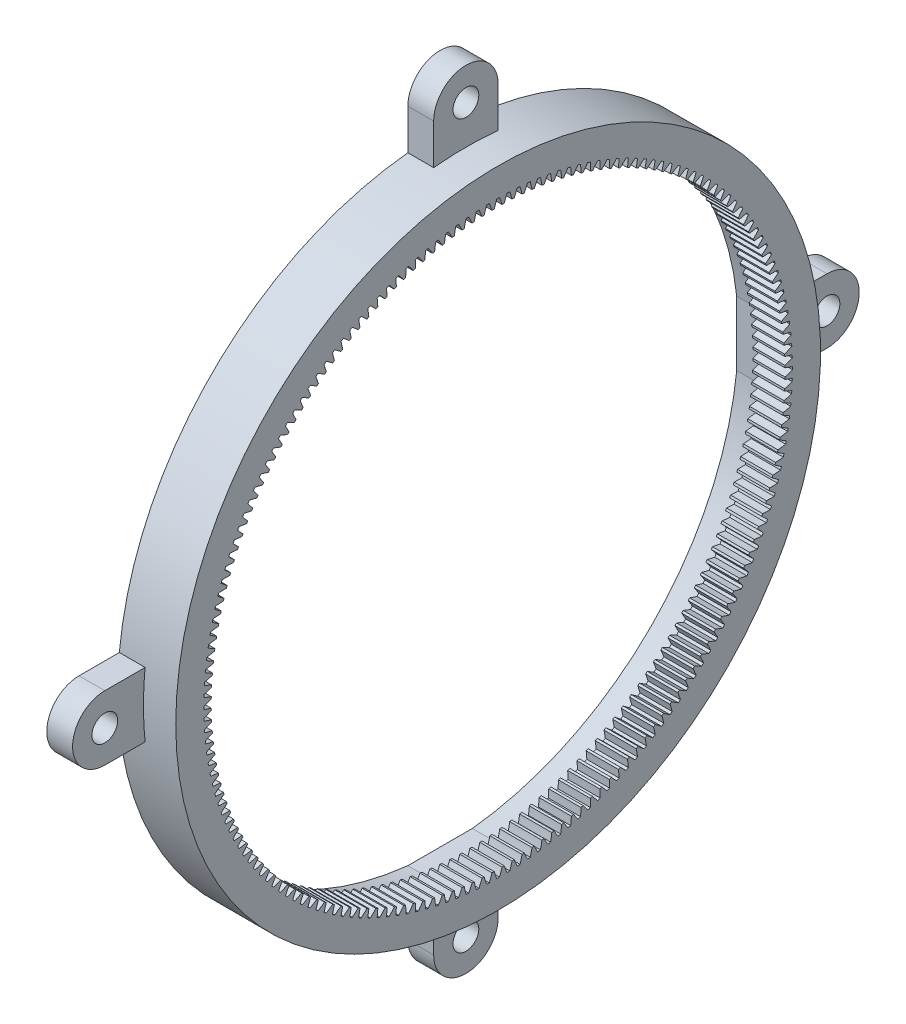
SolidWorks part; units mm, degrees
ref_plane "Plane1" through (0, 0, 0) normal (0, 0, 1) x (1, 0, 0)
ref_plane "Plane2" through (0, 0, 0) normal (0, 1, 0) x (1, 0, 0)
ref_plane "Plane3" through (0, 0, 0) normal (1, 0, 0) x (0, 0, -1)
other "Configuration Table"
sketch "HoldingSke" plane through (0, 0, 0) normal (0, 1, 0) x (1, 0, 0)
  line L0 (0, 0) -> (-1016, 0)
  line L1 (-15, 0) -> (100, 0) construction
  line L2 (0, 0) -> (-2.1039, 2.3779)
  line L3 (0, 0) -> (-11.863, 4.5341)
  line L4 (0, 0) -> (-8.636, 0)
  line L5 (0, 0) -> (-23.7986, -8.8762)
  line L6 (0, 0) -> (-10.5278, -7.1032)
  line L7 (-2.1039, 2.3779) -> (3.3635, 27.1825)
  line L8 (-76.2, 54.61) -> (-54.61, 54.61)
  line L9 (-71.009, 38.7566) -> (-53.1078, 45.2721)
  line L10 (-76.2, 71.12) -> (104.1128, 71.12)
  line L11 (0, 0) -> (-6.35, 0)
  line L12 (-76.2, 101.6) -> (-76.1746, 101.6)
  line L13 (24.9733, 27.94) -> (52.9518, 28.4284)
  line L14 (24.9733, 27.94) -> (25.0241, 27.9398)
  line L15 (24.9733, 27.94) -> (100.4021, 29.52)
  circle A0 centre (0, 0) radius 63.5
  circle A1 centre (0, 0) radius 12.7
  circle A2 centre (0, 0) radius 12.7
  dimension "Num_teeth" = 180
  dimension "Pitch_radius" = 180.3128
  dimension "Width" = 6.35
  dimension "Diameter" = 127
sketch "BasProSke" plane through (0, 0, 0) normal (0, 1, 0) x (1, 0, 0)
  line L0 (-10, 0) -> (60, 0) construction
  line L1 (0, 56.515) -> (0, 63.5)
  line L2 (0, 56.515) -> (6.35, 56.515)
  line L3 (6.35, 56.515) -> (6.35, 63.5)
  line L4 (6.35, 63.5) -> (0, 63.5)
  dimension "Thickness" = 6.35
  dimension "Diameter" = 127
revolve "Base-Revolve" add sketch "BasProSke" angle 360 about L0
sketch "TooCutSke" plane through (0, 0, 0) normal (1, 0, 0) x (0, 0, -1)
  line L3 (0.5622, 57.1472) -> (0.5622, 53.6633) construction
  line L4 (0, 0) -> (0, 59.563) construction
  line L5 (0, 0) -> (-1.1925, 68.3171) construction
  line L6 (-26.4678, 47.8785) -> (36.9935, 48.9862) construction
  circle A0 centre (0, 0) radius 57.15 construction
  circle A1 centre (0, 0) radius 57.9628 construction
  circle A2 centre (0, 0) radius 48.3331 construction
  circle A3 centre (0, 0) radius 56.4896 construction
  arc A4 (0.7806, 56.4842) -> (0.2689, 57.9622) centre (-26.4678, 47.8785) ccw
  arc A5 (0.7806, 56.4842) -> (-0.7806, 56.4842) centre (0, 0) ccw
  arc A6 (0.2689, 57.9622) -> (-0.2689, 57.9622) centre (0, 0) ccw
  arc A7 (-0.2689, 57.9622) -> (-0.7806, 56.4842) centre (26.4678, 47.8785) ccw
extrude "ToothCut" cut sketch "TooCutSke" along normal through all
fillet "Breaks" [suppressed] radius 0.0635
fillet "RootFillets" [suppressed] radius 0.1778
pattern_circular "TeethCuts" count 180 every 2 about axis through (-10, 0, 0) along (1, 0, 0) of "RootFillets", "Breaks", "ToothCut"
sketch "Sketch1" plane through (0, 0, 0) normal (-1, 0, 0) x (0, 0, 1)
  line L0 (-6.35, -58.42) -> (6.35, -58.42)
  line L1 (6.35, -63.1817) -> (6.35, -71.12)
  line L2 (-6.35, -71.12) -> (-6.35, -63.1817)
  line L3 (-71.12, 6.35) -> (-63.1817, 6.35)
  line L4 (-58.42, 6.35) -> (-58.42, -6.35)
  line L5 (-63.1817, -6.35) -> (-71.12, -6.35)
  line L6 (6.35, 71.12) -> (6.35, 63.1817)
  line L7 (6.35, 58.42) -> (-6.35, 58.42)
  line L8 (-6.35, 63.1817) -> (-6.35, 71.12)
  line L9 (71.12, -6.35) -> (63.1817, -6.35)
  line L10 (58.42, -6.35) -> (58.42, 6.35)
  line L11 (63.1817, 6.35) -> (71.12, 6.35)
  arc A0 (6.35, -71.12) -> (-6.35, -71.12) centre (0, -71.12) cw
  circle A1 centre (0, -71.12) radius 2.54
  arc A2 (-71.12, -6.35) -> (-71.12, 6.35) centre (-71.12, 0) cw
  circle A3 centre (-71.12, 0) radius 2.54
  arc A4 (-6.35, 71.12) -> (6.35, 71.12) centre (0, 71.12) cw
  circle A5 centre (0, 71.12) radius 2.54
  arc A6 (71.12, 6.35) -> (71.12, -6.35) centre (71.12, 0) cw
  circle A7 centre (71.12, 0) radius 2.54
  arc A9 (58.42, 6.35) -> (6.35, 58.42) centre (0, 0) ccw
  arc A11 (63.1817, 6.35) -> (6.35, 63.1817) centre (0, 0) ccw
  arc A13 (6.35, -63.1817) -> (63.1817, -6.35) centre (0, 0) ccw
  arc A14 (-63.1817, -6.35) -> (-6.35, -63.1817) centre (0, 0) ccw
  arc A15 (-6.35, 63.1817) -> (-63.1817, 6.35) centre (0, 0) ccw
  circle A16 centre (0, 0) radius 63.5 construction
  arc A17 (6.35, -58.42) -> (58.42, -6.35) centre (0, 0) ccw
  arc A19 (-58.42, -6.35) -> (-6.35, -58.42) centre (0, 0) ccw
  arc A21 (-6.35, 58.42) -> (-58.42, 6.35) centre (0, 0) ccw
  point P5 (0, -58.42)
  point P6 (-6.35, -67.1509)
  point P8 (6.35, -67.1509)
  point P31 (0, 0)
  point P32 (-6.35, 58.42)
  point P38 (6.35, 63.1817)
  point P43 (0, 0)
  point P44 (58.42, -42.3464)
  point P45 (58.42, -6.35)
  point P46 (0, 0)
  dimension "D2" = 58.42
  dimension "D4" = 5.08
  dimension "D1" = 12.7
  dimension "D3" = 12.7
  dimension "D5" = 4
extrude "Boss-Extrude1" add sketch "Sketch1" along normal blind 5.08
equation "' \"Pitch@HoldingSke\" = 4"
equation "' \"Num_teeth@HoldingSke\" = 24"
equation "' \"Ap@HoldingSke\" =  14.5"
equation "' \"Ap@HoldingSke\" = 14.5"
equation "' \"Width@HoldingSke\" = 0.5"
equation "' \"Diameter@HoldingSke\" = 8"
equation "' \"Show_teeth@HoldingSke\" = 100"
equation "' \"Backlash@HoldingSke\" = 0.009"
equation "' \"Addendum_fac@HoldingSke\" = 1.0"
equation "' \"Dedendum_fac@HoldingSke\" = 1.25"
equation "' \"Dedendum_add@HoldingSke\" = 0.00005"
equation "' \"Clearance_fac@HoldingSke\" = 0.25"
equation "\"Overcut_dia@TooCutSke\" = (\"Num_teeth@HoldingSke\" - 2 * \"Addendum_fac@HoldingSke\") / \"Pitch@HoldingSke\" - 0.002"
equation "\"Pitch_dia@TooCutSke\" = \"Num_teeth@HoldingSke\" / \"Pitch@HoldingSke\""
equation "\"Base_dia@TooCutSke\" = \"Num_teeth@HoldingSke\" / \"Pitch@HoldingSke\" * cos((\"Ap@HoldingSke\"  * 3.14159265 / 180)) * 0.90"
equation "\"Root_dia@TooCutSke\" = \"Num_teeth@HoldingSke\"  / \"Pitch@HoldingSke\" + 2 *  \"Dedendum_fac@HoldingSke\"/ \"Pitch@HoldingSke\" + \"Dedendum_add@HoldingSke\" * 2"
equation "\"Half_ang@TooCutSke\" = 180 / \"Num_teeth@HoldingSke\""
equation "\"Half_CT@TooCutSke\" = \"Num_teeth@HoldingSke\" / \"Pitch@HoldingSke\" * sin((3.14159265 / 2 / \"Num_teeth@HoldingSke\")) / 2 + 10 * \"Backlash@HoldingSke\" / 4"
equation "\"Flank_rad@TooCutSke\" = \"Num_teeth@HoldingSke\" / \"Pitch@HoldingSke\" / 4"
equation "\"Radius@RootFillets\"= \"Clearance_fac@HoldingSke\" / \"Pitch@HoldingSke\" + \"Dedendum_add@HoldingSke\""
equation "\"Break_rad@Breaks\" = 0.02 / \"Pitch@HoldingSke\" * 5"
equation "\"Num_teeth@TeethCuts\" = int( \"Show_teeth@HoldingSke\" ) + 1"
equation "\"Num_teeth@TeethCuts\" = ((sgn( \"Num_teeth@TeethCuts\" - \"Num_teeth@HoldingSke\" )-1)*( \"Num_teeth@TeethCuts\" - \"Num_teeth@HoldingSke\" ))/-2+ \"Num_teeth@HoldingSke\""
equation "\"Num_teeth@TeethCuts\" = ((sgn( \"Num_teeth@TeethCuts\" - 2.0)+1)*( \"Num_teeth@TeethCuts\" - 2.0))/2 +2.0"
equation "\"Angle@TeethCuts\" = 360.0 / \"Num_teeth@HoldingSke\""
equation "\"Diameter@BasProSke\" = \"Num_teeth@HoldingSke\"  / \"Pitch@HoldingSke\" + 2 *  \"Dedendum_fac@HoldingSke\"/ \"Pitch@HoldingSke\" + \"Dedendum_add@HoldingSke\" * 2 + 0.002"
equation "\"Diameter@BasProSke\" = ((sgn( \"Diameter@BasProSke\"  - \"Diameter@HoldingSke\" )+1)*( \"Diameter@BasProSke\"  - \"Diameter@HoldingSke\" ))/2 + \"Diameter@HoldingSke\""
equation "\"Inside_diameter@BasProSke\" =  (\"Num_teeth@HoldingSke\" - 2 * \"Addendum_fac@HoldingSke\") / \"Pitch@HoldingSke\" "
equation "\"Thickness@BasProSke\"  = \"Width@HoldingSke\""
